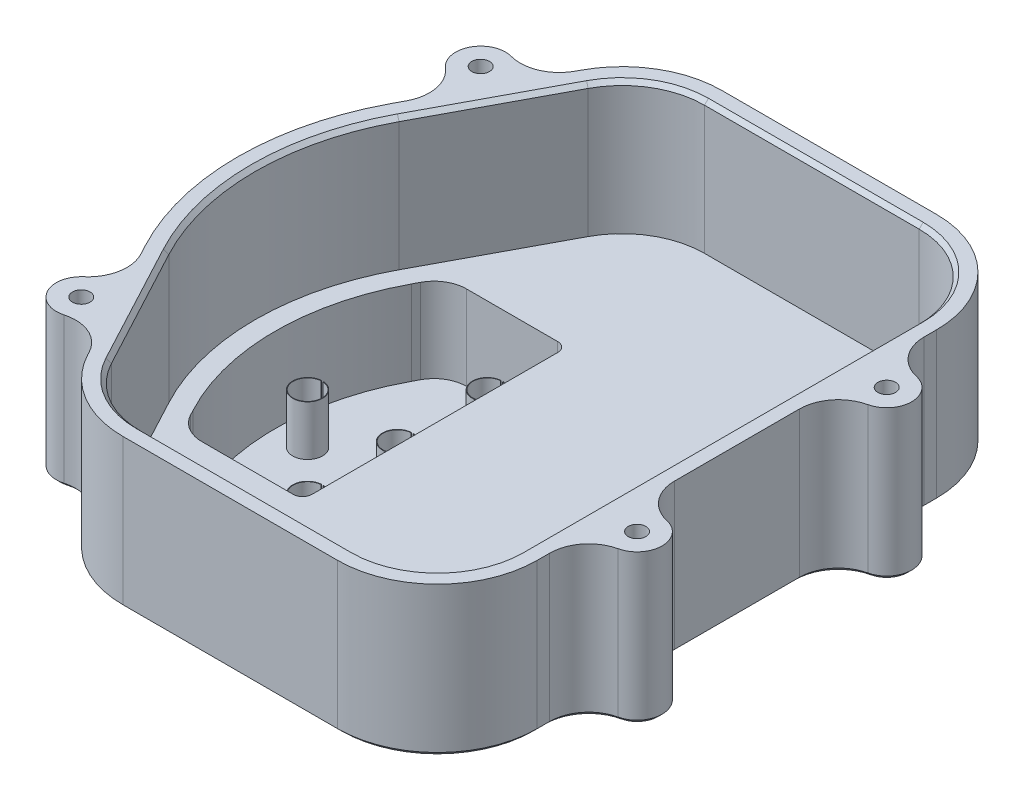
SolidWorks part; units mm, degrees
material "6061-T6 (SS)"
ref_plane "Front Plane" through (0, 0, 0) normal (0, 0, 1) x (1, 0, 0)
ref_plane "Top Plane" through (0, 0, 0) normal (0, 1, 0) x (1, 0, 0)
ref_plane "Right Plane" through (0, 0, 0) normal (1, 0, 0) x (0, 0, -1)
sketch "Sketch1" plane through (0, 0, 0) normal (0, 1, 0) x (1, 0, 0)
  line L0 (-57.15, 0) -> (-57.15, -50000) construction
  line L1 (-25.4, -76.2) -> (-25.4, -101.6) construction
  line L2 (-25.4, -76.2) -> (69.85, -76.2)
  line L3 (-25.4, 76.2) -> (69.85, 76.2)
  line L4 (69.85, -76.2) -> (69.85, 76.2)
  line L5 (-25.4, 76.2) -> (-25.4, 101.6) construction
  line L6 (0, 0) -> (0, -50000) construction
  line L7 (-49.3059, 31.3765) -> (-25.4, 76.2)
  line L8 (-57.15, 0) -> (69.85, 0) construction
  line L9 (-49.3059, -31.3765) -> (-25.4, -76.2)
  arc A0 (-49.3059, -31.3765) -> (-49.3059, 31.3765) centre (9.525, 0) cw
  point P0 (0, 0)
  dimension "D5" = 50.8
  dimension "D1" = 76.2
  dimension "D2" = 25.4
  dimension "D3" = 25.4
  dimension "D4" = 69.85
  dimension "D6" = 127
extrude "Boss-Extrude1" add sketch "Sketch1" along normal blind 38.1
fillet "Fillet1" radius 25.4 4 edges at (-25.4, 19.05, 76.2) (69.85, 19.05, 76.2) (69.85, 19.05, -76.2) (-25.4, 19.05, -76.2)
shell "Shell1" thickness 4.445 removed face at (4.3477, 38.1, 0)
sketch "Sketch13" plane through (0, 0, 0) normal (0, -1, 0) x (1, 0, 0)
  line L0 (0, 0) -> (-50000, 0) construction
  line L1 (-2.54, 38.1) -> (-2.54, -38.1)
  line L2 (-2.54, 38.1) -> (-40.2167, 38.1)
  line L3 (-49.3059, 31.3765) -> (-32.5718, 62.7529) construction
  line L4 (-40.2167, -38.1) -> (-2.54, -38.1)
  line L12 (-40.2167, -38.1) -> (-44.5994, -29.8824)
  line L13 (-44.5994, 29.8824) -> (-40.2167, 38.1)
  arc A1 (-49.3059, 31.3765) -> (-49.3059, -31.3765) centre (9.525, 0) ccw construction
  arc A5 (-44.5994, 29.8824) -> (-44.5994, -29.8824) centre (11.43, 0) ccw
  dimension "D3" = 49.53
  dimension "D2" = 63.5
  dimension "D5" = 54.61
  dimension "D1" = 76.2
extrude "nub" add sketch "Sketch13" along normal blind 23.368
fillet "Fillet2" radius 12.7 2 edges at (-40.2167, -11.684, -38.1) (-40.2167, -11.684, 38.1)
fillet "Fillet3" radius 6.858 2 edges at (-2.54, -11.684, -38.1) (-2.54, -11.684, 38.1)
sketch "Sketch8" plane through (0, 4.445, 0) normal (0, 1, 0) x (1, 0, 0)
  line L24 (-6.985, -31.242) -> (-6.985, 31.242)
  line L25 (-32.5967, -33.655) -> (-9.398, -33.655)
  line L26 (-40.6774, -27.7906) -> (-39.8805, -29.2847)
  line L27 (-39.8805, 29.2847) -> (-40.6774, 27.7906)
  line L28 (-32.5967, -33.655) -> (-9.398, -33.655)
  line L29 (-6.985, -31.242) -> (-6.985, 31.242)
  line L30 (-9.398, 33.655) -> (-32.5967, 33.655)
  line L31 (-40.6774, -27.7906) -> (-39.8805, -29.2847)
  line L32 (-39.8805, 29.2847) -> (-40.6774, 27.7906)
  line L33 (-9.398, 33.655) -> (-32.5967, 33.655)
  arc A30 (-6.985, 31.242) -> (-9.398, 33.655) centre (-9.398, 31.242) ccw
  arc A31 (-6.985, 31.242) -> (-9.398, 33.655) centre (-9.398, 31.242) ccw
  arc A32 (-40.6774, 27.7906) -> (-40.6774, -27.7906) centre (11.43, 0) ccw
  arc A33 (-39.8805, -29.2847) -> (-32.5967, -33.655) centre (-32.5967, -25.4) ccw
  arc A34 (-39.8805, -29.2847) -> (-32.5967, -33.655) centre (-32.5967, -25.4) ccw
  arc A35 (-32.5967, 33.655) -> (-39.8805, 29.2847) centre (-32.5967, 25.4) ccw
  arc A36 (-32.5967, 33.655) -> (-39.8805, 29.2847) centre (-32.5967, 25.4) ccw
  arc A37 (-40.6774, 27.7906) -> (-40.6774, -27.7906) centre (11.43, 0) ccw
  arc A38 (-9.398, -33.655) -> (-6.985, -31.242) centre (-9.398, -31.242) ccw
  arc A39 (-9.398, -33.655) -> (-6.985, -31.242) centre (-9.398, -31.242) ccw
  dimension "D1" = 4.445
extrude "Cut-Extrude1" cut sketch "Sketch8" against normal offset from surface (21.463 mm away) 6.35 up to face at (-27.2365, -23.368, 0)
chamfer "Chamfer1" distance 1.016 angle 45 10 edges at (-37.0168, 38.1, 44.9729) (-20.9413, 38.1, 68.7688) (-52.705, 38.1, 0) (17.145, 38.1, 71.755) (-37.0168, 38.1, -44.9729) (59.2674, 38.1, 65.6174) (-20.9413, 38.1, -68.7688) (65.405, 38.1, 0) (17.145, 38.1, -71.755) (59.2674, 38.1, -65.6174)
sketch "Sketch10" plane through (0, 38.1, 0) normal (0, 1, 0) x (1, 0, 0)
  line L0 (69.85, 47.625) -> (69.85, 15.875)
  line L1 (69.85, -50.8) -> (69.85, 50.8) construction
  line L2 (0, 0) -> (50000, 0) construction
  line L3 (69.85, -47.625) -> (69.85, -15.875)
  line L4 (-33.0698, 61.8191) -> (-48.011, 33.8044)
  line L5 (-32.5718, 62.7529) -> (-49.3059, 31.3765) construction
  line L6 (-44.4579, 56.9222) -> (-50.2886, 45.9897) construction
  line L7 (-42.0859, 47.888) -> (40559.6261, -29092.0967) construction
  line L8 (-44.4579, -56.9222) -> (-50.2886, -45.9897) construction
  line L9 (-33.0698, -61.8191) -> (-48.011, -33.8044)
  arc A0 (69.85, 47.625) -> (77.5939, 37.9451) centre (79.7719, 47.625) ccw
  arc A1 (77.5939, 37.9451) -> (77.5939, 25.5549) centre (76.2, 31.75) cw
  arc A2 (77.5939, -25.5549) -> (69.85, -15.875) centre (79.7719, -15.875) cw
  arc A3 (77.5939, 25.5549) -> (69.85, 15.875) centre (79.7719, 15.875) ccw
  arc A4 (77.5939, -37.9451) -> (77.5939, -25.5549) centre (76.2, -31.75) ccw
  arc A5 (69.85, -47.625) -> (77.5939, -37.9451) centre (79.7719, -47.625) cw
  arc A6 (-33.0698, 61.8191) -> (-44.4579, 56.9222) centre (-41.8244, 66.4882) cw
  arc A7 (-44.4579, 56.9222) -> (-50.2886, 45.9897) centre (-46.1433, 50.8) ccw
  arc A8 (-50.2886, 45.9897) -> (-48.011, 33.8044) centre (-56.7656, 38.4735) cw
  arc A9 (-50.2886, -45.9897) -> (-48.011, -33.8044) centre (-56.7656, -38.4735) ccw
  arc A10 (-44.4579, -56.9222) -> (-50.2886, -45.9897) centre (-46.1433, -50.8) cw
  arc A11 (-33.0698, -61.8191) -> (-44.4579, -56.9222) centre (-41.8244, -66.4882) ccw
  point P30 (-40.9388, 47.0647)
  dimension "D1" = 6.35
  dimension "D6" = 6.35
  dimension "D2" = 31.75
  dimension "D3" = 6.35
  dimension "D4" = 31.75
  dimension "D5" = 31.75
  dimension "D7" = 6.35
  dimension "D8" = 50.8
extrude "Boss-Extrude2" add sketch "Sketch10" against normal up to surface (38.1 mm away) up to face at (4.3477, 0, 0)
hole_wizard "#8 Clearance Hole1" positions "Sketch12" profile "Sketch11" hole size "#8" standard "Ansi Inch" end condition through all
sketch "Sketch12" plane through (0, 38.1, 0) normal (0, 1, 0) x (-1, 0, 0)
  arc A0 (44.4579, -56.9222) -> (50.2886, -45.9897) centre (46.1433, -50.8) ccw construction
  arc A1 (50.2886, 45.9897) -> (44.4579, 56.9222) centre (46.1433, 50.8) ccw construction
  arc A2 (-77.5939, 37.9451) -> (-77.5939, 25.5549) centre (-76.2, 31.75) ccw construction
  arc A3 (-77.5939, -25.5549) -> (-77.5939, -37.9451) centre (-76.2, -31.75) ccw construction
  point P0 (46.1433, -50.8)
  point P1 (46.1433, 50.8)
  point P3 (-76.2, 31.75)
  point P5 (-76.2, -31.75)
sketch "Sketch11" plane through (-46.1433, 38.1, -50.8) normal (1, 0, 0) x (0, 0, 1)
  line L0 (0, 0) -> (0, 61.468)
  line L1 (0, 61.468) -> (2.2479, 61.468)
  line L2 (2.2479, 61.468) -> (2.2479, 0)
  line L5 (2.2479, 0) -> (0, 0)
  line L11 (0, -6.35) -> (0, 107.95) construction
  dimension "Thru Hole Dia." = 4.4958
  dimension "Thru Hole Depth" = 61.468
chamfer "Chamfer2" distance 1.016 angle 45 36 edges at (-32.8208, 0, 62.286) (-23.2282, 0, 72.5803) (17.145, 0, 76.2) (62.4105, 0, 68.7605) (69.85, 0, 49.2125) (69.85, 0, -49.2125) (-32.8208, 0, -62.286) (62.4105, 0, -68.7605) (-23.2282, 0, -72.5803) (17.145, 0, -76.2) (-37.905, 0, 57.3733) (-51.7463, 0, 53.7882) (72.0242, 0, 41.4269) (-47.0126, 0, 40.2965) (82.55, 0, 31.75) (-48.6584, 0, 32.5904) (72.0242, 0, 22.0731) (69.85, 0, 0) (-48.6584, 0, -32.5904) (72.0242, 0, -22.0731) (-47.0126, 0, -40.2965) (82.55, 0, -31.75) (-51.7463, 0, -53.7882) (72.0242, 0, -41.4269) (-37.905, 0, -57.3733) (-57.15, 0, 0) (-2.54, -23.368, 0) (-20.9973, -23.368, 38.1) (-20.9973, -23.368, -38.1) (-39.1308, -23.368, 36.2902) (-39.1308, -23.368, -36.2902) (-44.201, -23.368, 30.6294) (-44.201, -23.368, -30.6294) (-52.07, -23.368, 0) (-4.5487, -23.368, 36.0913) (-4.5487, -23.368, -36.0913)
sketch "Sketch14" plane through (0, -23.368, 0) normal (0, -1, 0) x (1, 0, 0)
  line L0 (0, 0) -> (50000, 0) construction
  line L1 (-2.54, -31.242) -> (-2.54, 31.242) construction
  circle A0 centre (-16.51, 22.86) radius 3.675
  circle A1 centre (-16.51, 0) radius 3.675
  circle A2 centre (-16.51, -22.86) radius 3.675
  circle A3 centre (-39.37, 0) radius 3.675
  dimension "D1" = 7.35
  dimension "D2" = 45.72
  dimension "D3" = 22.86
  dimension "D4" = 13.97
extrude "Cut-Extrude2" cut sketch "Sketch14" against normal through all
ref_point "Point1"
ref_plane "Plane1" through (-16.51, 0, 0) normal (-1, 0, 0) x (0, 0, 1)
ref_point "Point2"
ref_point "Point3"
ref_point "Point4"
sketch "Sketch16" plane through (0, -17.018, 0) normal (0, 1, 0) x (1, 0, 0)
  circle A0 centre (-16.51, -22.86) radius 3.6754
  circle A1 centre (-16.51, -22.86) radius 3.8024
  dimension "D1" = 7.3508
  dimension "D2" = 7.6048
extrude "Boss-Extrude3" add sketch "Sketch16" along normal blind 12.7
ref_plane "Plane2" through (0, 0, 19.0576) normal (0, 0, -1) x (-1, 0, 0)
sketch "Sketch17" plane through (0, 0, 19.0576) normal (0, 0, -1) x (-1, 0, 0)
  line L0 (20.3124, -4.318) -> (12.7076, -4.318) construction
  line L1 (16.256, -4.318) -> (16.256, -11.938)
  line L2 (16.764, -4.318) -> (16.764, -11.938)
  line L3 (16.256, -11.938) -> (16.764, -11.938)
  line L4 (16.256, -4.318) -> (16.764, -4.318)
  point P0 (16.51, -4.318)
  point P3 (16.764, -4.318)
  point P5 (16.256, -4.318)
  dimension "D1" = 0.254
  dimension "D2" = 0.254
  dimension "D3" = 7.62
extrude "Cut-Extrude4" cut sketch "Sketch17" against normal blind 2.54 contours L1 L3 L2 L4
pattern_linear "LPattern1" count 3 spacing 22.86 along (0, 0, -1) count 2 spacing 22.86 along (-1, 0, 0) skipping (0, 1), (2, 1) of "Boss-Extrude3", "Cut-Extrude4"
